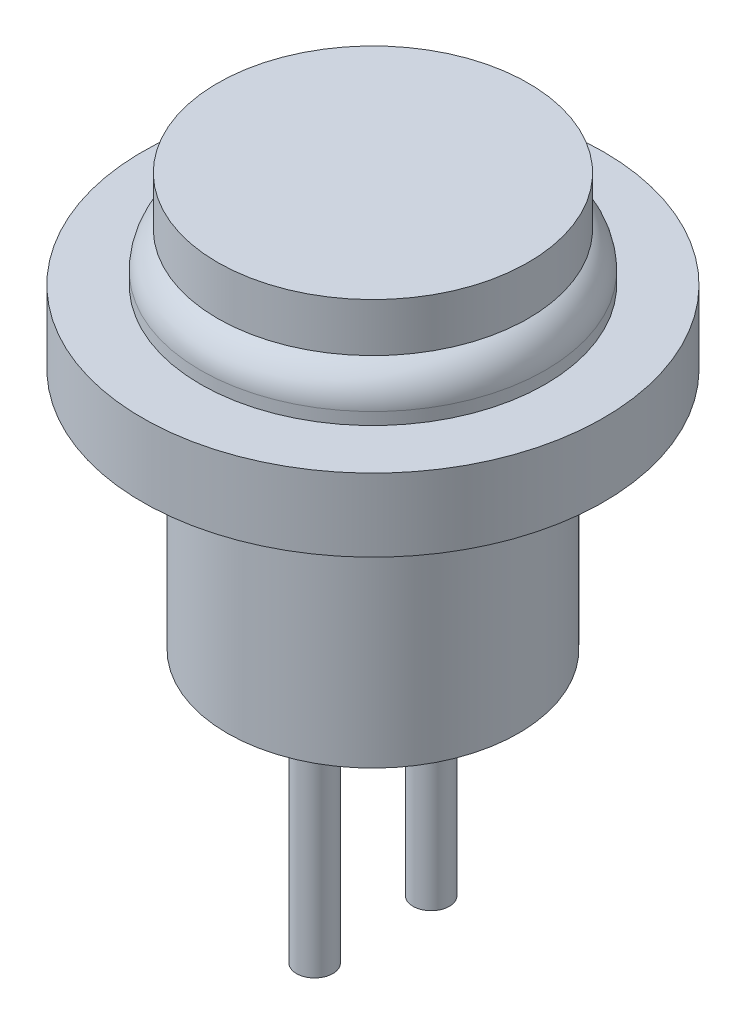
SolidWorks part; units mm, degrees
ref_plane "前视基准面" through (0, 0, 0) normal (0, 0, 1) x (1, 0, 0)
ref_plane "上视基准面" through (0, 0, 0) normal (0, 1, 0) x (1, 0, 0)
ref_plane "右视基准面" through (0, 0, 0) normal (1, 0, 0) x (0, 0, -1)
sketch "草图1" plane through (0, 0, 0) normal (0, 1, 0) x (1, 0, 0)
  circle A0 centre (0, 0) radius 7.1
  dimension "D1" = 14.2
extrude "拉伸1" add sketch "草图1" along normal blind 2
fillet "圆角1" radius 1.5 1 edges at (0, 2, 7.1)
sketch "草图2" plane through (0, 2, 0) normal (0, 1, 0) x (-1, 0, 0)
  circle A0 centre (0, 0) radius 6.4
  dimension "D1" = 12.8
extrude "拉伸2" add sketch "草图2" along normal blind 2
sketch "草图3" plane through (0, 0, 0) normal (0, -1, 0) x (1, 0, 0)
  circle A0 centre (0, 0) radius 6
  dimension "D1" = 12
extrude "拉伸3" add sketch "草图3" along normal blind 13
sketch "草图4" plane through (0, -13, 0) normal (0, -1, 0) x (1, 0, 0)
  line L0 (0, 5.4821) -> (0, -6.0169) construction
  circle A0 centre (0, -2.4) radius 0.75
  circle A1 centre (0, 2.4) radius 0.75
  dimension "D1" = 1.5
  dimension "D2" = 1.5
  dimension "D3" = 2.4
  dimension "D4" = 2.4
extrude "拉伸4" add sketch "草图4" along normal blind 10
ref_plane "基准面1" through (0, -1, 0) normal (0, -1, 0) x (1, 0, 0)
sketch "草图5" plane through (0, 0, 0) normal (0, -1, 0) x (1, 0, 0)
  circle A0 centre (0, 0) radius 6
  circle A1 centre (0, 0) radius 6 construction
  circle A2 centre (0, 0) radius 9.5
  dimension "D1" = 19
extrude "拉伸5" add sketch "草图5" along normal blind 3
